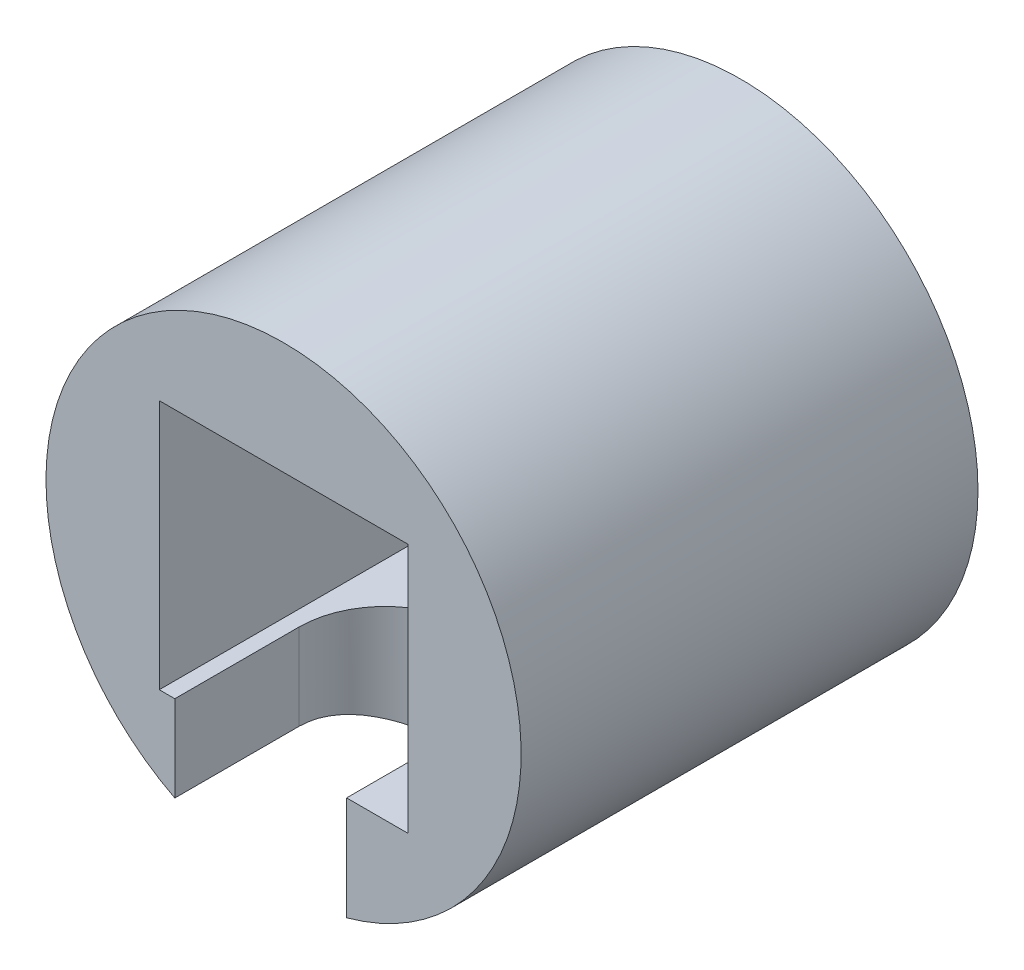
SolidWorks part; units mm, degrees
ref_plane "Front Plane" through (0, 0, 0) normal (0, 0, 1) x (1, 0, 0)
ref_plane "Top Plane" through (0, 0, 0) normal (0, 1, 0) x (1, 0, 0)
ref_plane "Right Plane" through (0, 0, 0) normal (1, 0, 0) x (0, 0, -1)
sketch "Sketch1" plane through (0, 0, 0) normal (0, 0, 1) x (1, 0, 0)
  circle A1 centre (0, 0) radius 3
  circle A2 centre (0, 0) radius 13
extrude "Boss-Extrude1" add sketch "Sketch1" along normal blind 25
sketch "Sketch2" plane through (0, 0, 0) normal (0, 1, 0) x (1, 0, 0)
  line L4 (-6.8, -25) -> (6.8, -25)
  line L5 (-6.8, -11.3) -> (6.8, -11.3)
  line L6 (-6.8, -11.3) -> (-6.8, -25)
  line L7 (6.8, -25) -> (6.8, -11.3)
extrude "Cut-Extrude1" cut sketch "Sketch2" against normal mid plane 13.7
sketch "Sketch3" plane through (0, 0, 0) normal (0, 1, 0) x (1, 0, 0)
  line L6 (-5.95, -18.2) -> (-5.95, -25)
  line L7 (-5.95, -25) -> (3.45, -25)
  line L8 (3.45, -18.2) -> (3.45, -25)
  arc A1 (3.45, -18.2) -> (-5.95, -18.2) centre (-1.25, -18.2) ccw
extrude "Cut-Extrude2" cut sketch "Sketch3" against normal up to surface (12.5339 mm away) up to face at (13, 0, 25)
